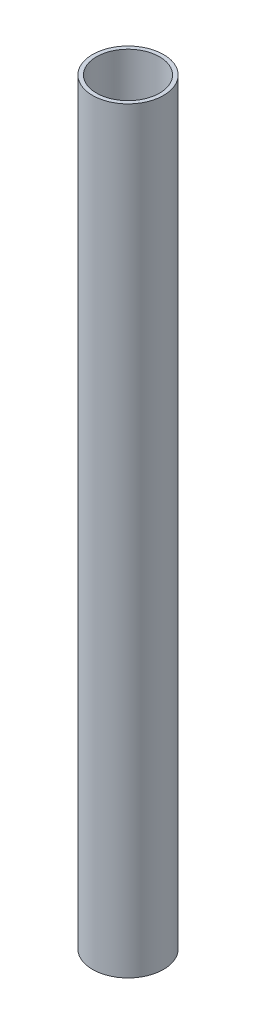
SolidWorks part; units mm, degrees
ref_plane "Front Plane" through (0, 0, 0) normal (0, 0, 1) x (1, 0, 0)
ref_plane "Top Plane" through (0, 0, 0) normal (0, 1, 0) x (1, 0, 0)
ref_plane "Right Plane" through (0, 0, 0) normal (1, 0, 0) x (0, 0, -1)
sketch "Sketch1" plane through (0, 0, 0) normal (0, 1, 0) x (1, 0, 0)
  circle A0 centre (0, 0) radius 50.8
  circle A1 centre (0, 0) radius 57.15
  dimension "D1" = 101.6
  dimension "D2" = 114.3
extrude "Boss-Extrude1" add sketch "Sketch1" along normal mid plane 1219.2
